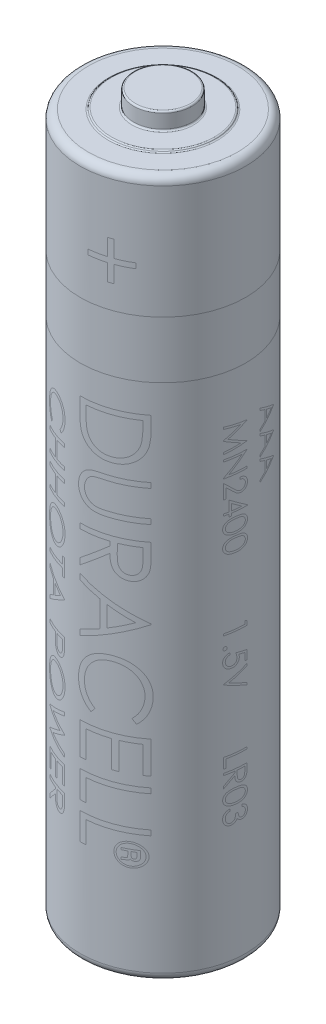
SolidWorks part; units mm, degrees
ref_plane "Front Plane" through (0, 0, 0) normal (0, 0, 1) x (1, 0, 0)
ref_plane "Top Plane" through (0, 0, 0) normal (0, 1, 0) x (1, 0, 0)
ref_plane "Right Plane" through (0, 0, 0) normal (1, 0, 0) x (0, 0, -1)
sketch "Sketch1" plane through (0, 0, 0) normal (0, 1, 0) x (1, 0, 0)
  circle A0 centre (0, 0) radius 5.1
  dimension "D1" = 10.2
extrude "Boss-Extrude1" add sketch "Sketch1" along normal blind 43 contours A0
sketch "Sketch2" plane through (0, 43, 0) normal (0, 1, 0) x (1, 0, 0)
  circle A0 centre (0, 0) radius 1.8
  dimension "D1" = 3.6
extrude "Boss-Extrude2" add sketch "Sketch2" along normal blind 1.15
fillet "Fillet1" radius 0.1 1 edges at (0, 44.15, 1.8)
sketch "Sketch3" plane through (0, 43, 0) normal (0, 1, 0) x (1, 0, 0)
  circle A0 centre (0, 0) radius 3.25
  dimension "D1" = 6.5
extrude "Boss-Extrude3" add sketch "Sketch3" along normal blind 0.1 contours A0
fillet "Fillet2" radius 0.1 2 edges at (0, 43, 3.25) (0, 43.1, 1.8)
fillet "Fillet3" radius 0.1 1 edges at (0, 43.1, 3.25)
fillet "Fillet4" radius 0.5 2 edges at (0, 0, 5.1) (0, 43, 5.1)
sketch "Sketch4" plane through (0, 0, 0) normal (0, -1, 0) x (1, 0, 0)
  circle A0 centre (0, 0) radius 3
  dimension "D1" = 6
extrude "Boss-Extrude4" add sketch "Sketch4" along normal blind 0.1
fillet "Fillet5" radius 0.5 1 edges at (0, 0, 3)
fillet "Fillet6" radius 0.5 1 edges at (0, -0.1, -3)
sketch "Sketch5" plane through (0, 0, 0) normal (0, 0, 1) x (1, 0, 0)
  line L0 (4.6, 43) -> (-4.6, 43) construction
  line L1 (-16.5, 35.5) -> (16.5, 35.5)
  line L2 (-16.5, 35.5) -> (-16.5, 32)
  line L3 (-16.5, 32) -> (16.5, 32)
  line L4 (16.5, 35.5) -> (16.5, 32)
  line L5 (0, 42.5) -> (0, 21.4188) construction
  line L6 (-5.1, 42.5) -> (5.1, 42.5) construction
  dimension "D1" = 3.5
  dimension "D2" = 7.5
  dimension "D3" = 33
split line "Split Line1"
sketch "Sketch6" plane through (0, 0, 0) normal (0, 0, 1) x (1, 0, 0)
  line L0 (-0.0101, 30.8963) -> (-0.0101, 6.086) construction
  line L2 (-2.6761, 30.5154) -> (-2.6761, 6.086) construction
  text T0 "DURACELL"
  text T1 "CHHOTA POWER" font "Century Gothic" height in points 6
wrap "Wrap2" sketch "Sketch6" wrap type scribe source sketch "Sketch6" face at (0, 0.5, 5.1)
sketch "Sketch9" plane through (0, 0, 0) normal (0, 0, 1) x (1, 0, 0)
  line L0 (-0.0873, 41.9376) -> (-0.0873, 34.3077) construction
  text T0 "+"
  point P4 (-0.7566, 34.3077)
  point P5 (-0.6227, 41.9376)
wrap "Wrap3" sketch "Sketch9" wrap type scribe source sketch "Sketch9" face at (0, 42.5, 5.1)
sketch "Sketch10" plane through (0, 0, 0) normal (0, 0, 1) x (1, 0, 0)
  line L0 (1.7794, 9.2097) -> (1.7794, 4.1484) construction
  text T0 "®" font "Century Gothic" height in points 5
  point P3 (2.3041, 8.6851)
  point P4 (0, 0)
  point P5 (2.3041, 9.2097)
  point P6 (1.5017, 4.1484)
split line "Split Line2"
ref_plane "Plane3" through (0, 0, -8.5) normal (0, 0, 1) x (1, 0, 0)
sketch "Sketch13" plane through (0, 0, -8.5) normal (0, 0, 1) x (1, 0, 0)
  line L0 (0, 2.0971) -> (0, 32.8411) construction
  line L1 (2.4662, 2.0971) -> (2.4662, 32.8411) construction
  text T0 "DURACELL\r\n"
  text T1 "CHHOTA POWER" font "Century Gothic" height in points 6
wrap "Wrap8" sketch "Sketch13" wrap type scribe source sketch "Sketch13" face at (-1.7287, 11.5494, 4.7454)
sketch "Sketch14" plane through (0, 0, 0) normal (0, 0, 1) x (1, 0, 0)
  line L0 (-1.6566, 7.634) -> (-1.6566, 3.8483) construction
  text T0 "®" font "Century Gothic" height in points 5
split line "Split Line3"
sketch "Sketch15" plane through (0, 0, 0) normal (1, 0, 0) x (0, 0, -1)
  line L0 (-1.2455, 30.4812) -> (-1.2455, 6.4236) construction
  line L1 (0.9833, 30.4812) -> (0.9833, 23.5983) construction
  text T0 "MN2400       1.5V      LR03" font "Century Gothic" height in points 5
  text T1 "AAA" font "Century Gothic" height in points 5
  point P7 (0.9833, 23.5983)
wrap "Wrap9" sketch "Sketch15" wrap type scribe source sketch "Sketch15" face at (1.6798, 27.4955, -4.7832)
sketch "Sketch16" plane through (0, 0, 0) normal (1, 0, 0) x (0, 0, -1)
  line L0 (-2.324, 29.268) -> (-2.324, 2.6694) construction
  line L1 (-1.1499, 29.268) -> (-1.1499, 2.6694) construction
  line L2 (0.1597, 26.0166) -> (0.1597, 2.6694) construction
  line L3 (1.6048, 26.0166) -> (1.6048, 2.6694) construction
  line L4 (2.9596, 29.268) -> (2.9596, 2.6694) construction
  text T0 "ALKALINE                       Made in China" font "Century Gothic" height in points 3
  text T1 "CAUTION: Do not connect improperly," font "Century Gothic" height in points 3
  text T2 "charge or dispose of in fire" font "Century Gothic" height in points 3
  text T3 "Battery may explode or leak." font "Century Gothic" height in points 3
  text T4 "FOR SALE IN SAARC COUNTRIES ONLY" font "Century Gothic" height in points 3
  point P10 (-1.2402, 2.6694)
  point P11 (-2.6401, 2.6694)
  point P14 (1.9661, 26.0166)
  point P15 (0.6565, 26.0166)
split line "Split Line4"
